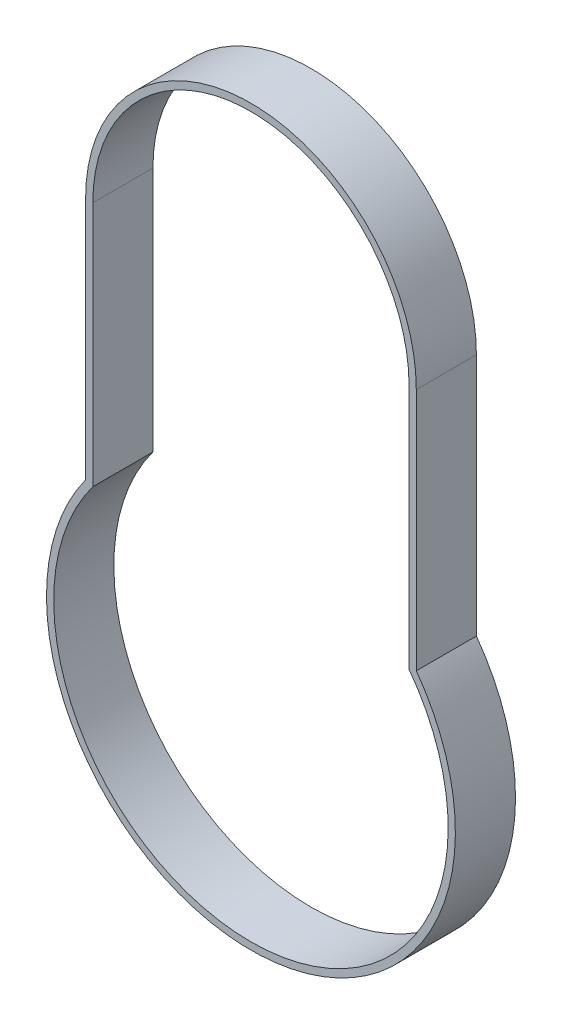
SolidWorks part; units mm, degrees
ref_plane "Plan de face" through (0, 0, 0) normal (0, 0, 1) x (1, 0, 0)
ref_plane "Plan de dessus" through (0, 0, 0) normal (0, 1, 0) x (1, 0, 0)
ref_plane "Plan de droite" through (0, 0, 0) normal (1, 0, 0) x (0, 0, -1)
sketch "Esquisse1" plane through (0, 0, 0) normal (0, 0, 1) x (1, 0, 0)
  line L0 (-26.3, -40.9003) -> (-26.3, 0)
  line L1 (26.3, 0) -> (26.3, -40.9003)
  line L2 (0, 26.3) -> (0, -93.3) construction
  arc A0 (-26.3, 0) -> (26.3, 0) centre (0, 0) cw
  arc A2 (-26.3, -40.9003) -> (26.3, -40.9003) centre (0, -60.5) ccw
  point P0 (0, -26.0589)
  dimension "D2" = 65.6
  dimension "D1" = 52.6
  dimension "D3" = 119.6
extrude "Extru.-Mince1" add sketch "Esquisse1" along normal blind 10 thin thin type one direction wall 1.2
